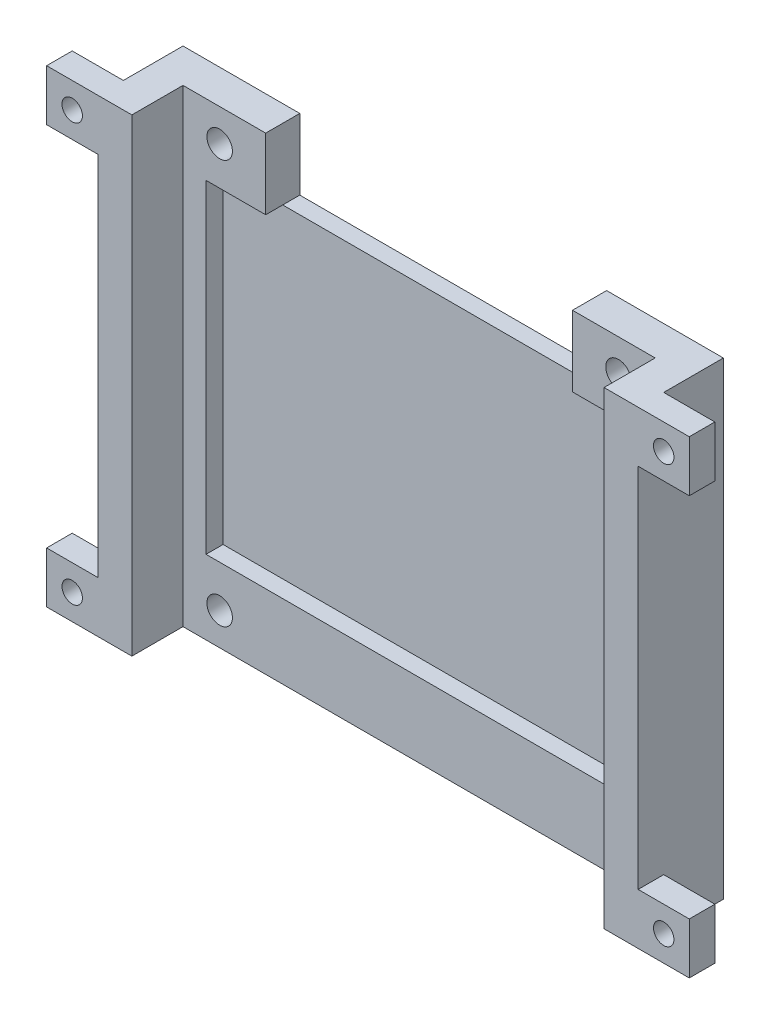
SolidWorks part; units mm, degrees
ref_plane "前视基准面" through (0, 0, 0) normal (0, 0, 1) x (1, 0, 0)
ref_plane "上视基准面" through (0, 0, 0) normal (0, 1, 0) x (1, 0, 0)
ref_plane "右视基准面" through (0, 0, 0) normal (1, 0, 0) x (0, 0, -1)
other "Configuration Table"
sketch "草图1" plane through (0, 0, 0) normal (0, 0, 1) x (1, 0, 0)
  line L9 (-13.85, 13.75) -> (13.85, 13.75)
  line L10 (-13.85, 13.75) -> (-13.85, -13.75)
  line L11 (-13.85, -13.75) -> (13.85, -13.75)
  line L12 (13.85, 13.75) -> (13.85, -13.75)
  line L13 (-13.85, 13.75) -> (-15.85, 13.75)
  line L14 (-13.85, 13.75) -> (-13.85, -13.75)
  line L15 (-13.85, -13.75) -> (-15.85, -13.75)
  line L16 (-15.85, 13.75) -> (-15.85, -13.75)
  line L17 (13.85, -13.75) -> (15.85, -13.75)
  line L18 (13.85, -13.75) -> (13.85, 13.75)
  line L19 (13.85, 13.75) -> (15.85, 13.75)
  line L20 (15.85, -13.75) -> (15.85, 13.75)
  line L21 (-15.85, 13.75) -> (-18.85, 13.75)
  line L42 (-15.85, 13.75) -> (-15.85, 10.75)
  line L43 (-15.85, 10.75) -> (-18.85, 10.75)
  line L44 (-18.85, 13.75) -> (-18.85, 10.75)
  line L45 (-15.85, -13.75) -> (-18.85, -13.75)
  line L46 (-15.85, -13.75) -> (-15.85, -10.75)
  line L47 (-15.85, -10.75) -> (-18.85, -10.75)
  line L48 (-18.85, -13.75) -> (-18.85, -10.75)
  line L49 (15.85, -13.75) -> (18.85, -13.75)
  line L50 (15.85, -13.75) -> (15.85, -10.75)
  line L51 (15.85, -10.75) -> (18.85, -10.75)
  line L52 (18.85, -13.75) -> (18.85, -10.75)
  line L53 (15.85, 13.75) -> (18.85, 13.75)
  line L54 (15.85, 13.75) -> (15.85, 10.75)
  line L55 (15.85, 10.75) -> (18.85, 10.75)
  line L56 (18.85, 13.75) -> (18.85, 10.75)
  circle A12 centre (-17.35, 12.25) radius 0.6
  circle A13 centre (-17.35, -12.25) radius 0.6
  circle A14 centre (17.35, -12.25) radius 0.6
  circle A15 centre (17.35, 12.25) radius 0.6
  point P4 (0, 13.75)
  point P6 (-13.85, 0)
  point P32 (-17.35, 13.75)
  point P33 (-18.85, 12.25)
  point P35 (18.85, -12.25)
  point P37 (17.35, -13.75)
  dimension "D4" = 3
  dimension "D1" = 27.5
  dimension "D2" = 27.7
  dimension "D3" = 2
  dimension "D6" = 1.2
  dimension "D5" = 3
extrude "凸台-拉伸1" add sketch "草图1" along normal blind 2 contours L11 L12 L9 L10
extrude "凸台-拉伸2" add sketch "草图1<13>" along normal blind 5 contours L13 L16 L15 L10 | L17 L20 L19 L12 region at (-14.85, 0, 0) region at (14.85, 0, 0)
sketch "草图1<13>" plane through (0, 0, 0) normal (0, 0, 1) x (1, 0, 0) same geometry as "草图1"
sketch "草图2" plane through (0, 0, 2) normal (0, 0, 1) x (1, 0, 0)
  line L1 (-9, 9.6) -> (9, 9.6)
  line L2 (-9, 9.6) -> (-9, 13.75)
  line L3 (-9, 13.75) -> (9, 13.75)
  line L4 (9, 9.6) -> (9, 13.75)
  line L5 (-13.85, 13.75) -> (13.85, 13.75) construction
  line L7 (-12.5, 9.6) -> (12.5, 9.6)
  line L8 (-12.5, 9.6) -> (-12.5, -9.4)
  line L9 (-12.5, -9.4) -> (12.5, -9.4)
  line L10 (12.5, 9.6) -> (12.5, -9.4)
  circle A0 centre (-11.7, 11.85) radius 0.75
  circle A1 centre (11.7, 11.85) radius 0.75
  circle A2 centre (-11.7, -11.85) radius 0.75
  circle A3 centre (11.7, -11.85) radius 0.75
  point P4 (0, 13.75)
  point P5 (0, 0)
  point P16 (-8.0982, 15.8735)
  point P17 (-11.541, 11.85)
  point P23 (11.7, -11.85)
  point P24 (0, 0)
  point P30 (0, -9.4)
  dimension "D3" = 1.5
  dimension "D1" = 4.15
  dimension "D2" = 18
  dimension "D4" = 25
  dimension "D5" = 19
extrude "切除-拉伸1" cut sketch "草图2" against normal through all contours A0 | L2 L3 L4 L1 | A1 | A3 | A2
extrude "切除-拉伸2" cut sketch "草图2<3>" against normal blind 1 contours L9 L10 L7 L8
sketch "草图2<3>" plane through (0, 0, 2) normal (0, 0, 1) x (1, 0, 0) same geometry as "草图2"
extrude "凸台-拉伸3" add sketch "草图1<14>" against normal blind 1.5 from surface contours L21 L44 L43 L16 A12 | L48 L45 L16 L47 A13 | L49 L52 L51 L20 A14 | L56 L53 L20 L55 A15 region at (-15.8924, 12.25, 0) region at (17.35, 13.7076, 0) region at (-17.35, -13.7076, 0) region at (15.8924, -12.25, 0) starting at face at (14.85, 0, 5)
sketch "草图1<14>" plane through (0, 0, 0) normal (0, 0, 1) x (1, 0, 0) same geometry as "草图1"
